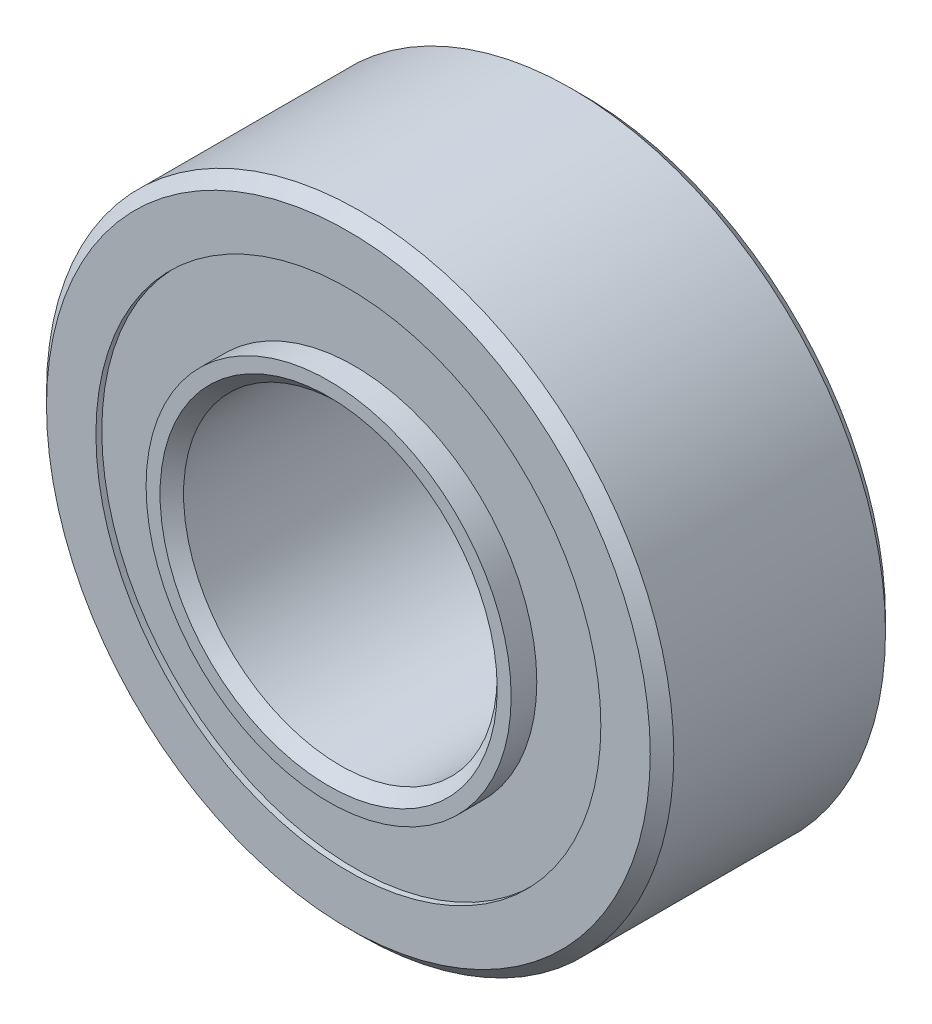
SolidWorks part; units mm, degrees
ref_plane "Front Plane" through (0, 0, 0) normal (0, 0, 1) x (1, 0, 0)
ref_plane "Top Plane" through (0, 0, 0) normal (0, 1, 0) x (1, 0, 0)
ref_plane "Right Plane" through (0, 0, 0) normal (1, 0, 0) x (0, 0, -1)
sketch "Sketch1" plane through (0, 0, 0) normal (1, 0, 0) x (0, 0, -1)
  line L0 (-2.3813, 0) -> (2.3813, 0) construction
  line L1 (0, 6.35) -> (0, -6.35) construction
  line L2 (2.1431, 6.35) -> (-2.1431, 6.35)
  line L3 (-2.1431, 6.35) -> (-2.3813, 6.1119)
  line L4 (-2.3813, 6.1119) -> (-2.3813, 5.1114)
  line L5 (-2.3813, 5.1114) -> (-1.0583, 5.1114)
  line L6 (2.3813, 5.1114) -> (1.0583, 5.1114)
  line L7 (2.3813, 6.1119) -> (2.3813, 5.1114)
  line L8 (2.1431, 6.35) -> (2.3813, 6.1119)
  line L9 (0, 6.35) -> (0, 4.7625) construction
  line L10 (0, 4.7625) -> (0, 3.175) construction
  arc A0 (-1.0583, 5.1114) -> (1.0583, 5.1114) centre (0, 4.7625) cw
  point P14 (0, 3.175)
  dimension "Width" = 4.7625
  dimension "OD" = 12.7
  dimension "D1" = 45
  dimension "D2" = 0.2381
  dimension "Shaft Dia" = 6.35
  dimension "D3" = 2.1167
  dimension "D4" = 0.3489
revolve "Revolve1" add sketch "Sketch1" angle 360 about L0
sketch "Sketch3" plane through (0, 0, 0) normal (1, 0, 0) x (0, 0, -1)
  line L0 (-1.0583, 4.4136) -> (-2.7813, 4.4136) construction
  line L1 (-2.3813, 6.1119) -> (-2.3813, 5.1114) construction
  line L2 (-2.1431, 6.35) -> (-2.3813, 6.1119) construction
  line L3 (-2.7813, 4.4136) -> (-2.7813, 3.4131) construction
  line L4 (-2.7813, 3.4131) -> (-2.7813, 3.6957)
  line L5 (-2.7813, 3.4131) -> (-2.5432, 3.175)
  line L6 (-2.5432, 3.175) -> (2.5432, 3.175)
  line L7 (-2.7813, 3.6957) -> (2.7813, 3.6957)
  line L8 (2.5432, 3.175) -> (2.7813, 3.4131)
  line L9 (-1.5875, 0) -> (1.3916, 0) construction
  line L10 (2.7813, 3.4131) -> (2.7813, 4.4136) construction
  line L11 (2.7813, 4.4136) -> (1.0583, 4.4136) construction
  line L12 (0, 6.35) -> (0, -6.35) construction
  line L13 (2.1431, 6.35) -> (2.3813, 6.1119) construction
  line L18 (2.7813, 3.6957) -> (2.7813, 3.4131)
  arc A1 (1.0583, 4.4136) -> (-1.0583, 4.4136) centre (0, 4.7625) cw construction
  arc A2 (1.0583, 5.1114) -> (-1.0583, 5.1114) centre (0, 4.7625) ccw construction
  dimension "D1" = 45
  dimension "Ring" = 5.5626
  dimension "D2" = 7.3914
revolve "Revolve3" add sketch "Sketch3" angle 360 about L0
sketch "Sketch4" plane through (0, 0, 0) normal (1, 0, 0) x (0, 0, -1)
  line L0 (-1.1144, 4.7625) -> (1.1144, 4.7625)
  arc A2 (-1.1144, 4.7625) -> (1.1144, 4.7625) centre (0, 4.7625) cw
  arc A3 (1.0583, 5.1114) -> (-1.0583, 5.1114) centre (0, 4.7625) ccw construction
revolve "Revolve4" add sketch "Sketch4" angle 360 about L0
ref_axis "Axis1" through (0, 0, -2.3813) along (0, 0, 1)
pattern_circular "CirPattern1" count 10 every 36 about axis through (0, 0, -2.3813) along (0, 0, 1) of bodies 104
sketch "Sketch5" plane through (0, 0, 0) normal (1, 0, 0) x (0, 0, -1)
  line L0 (-2.3813, 5.1114) -> (-1.0583, 5.1114) construction
  line L1 (-2.2622, 5.1114) -> (-1.1144, 5.1114)
  line L2 (-2.2622, 5.1114) -> (-2.2622, 3.6957)
  line L3 (-2.2622, 3.6957) -> (-1.1144, 3.6957)
  line L4 (-1.1144, 5.1114) -> (-1.1144, 3.6957)
  line L5 (-2.7813, 3.6957) -> (2.7813, 3.6957) construction
  line L6 (2.3813, 5.1114) -> (1.0583, 5.1114) construction
  line L7 (2.2622, 5.1114) -> (1.1144, 5.1114)
  line L8 (2.2622, 5.1114) -> (2.2622, 3.6957)
  line L9 (2.2622, 3.6957) -> (1.1144, 3.6957)
  line L10 (1.1144, 5.1114) -> (1.1144, 3.6957)
  line L12 (-2.1431, 6.35) -> (-2.3813, 6.1119) construction
  point P18 (-2.2622, 6.2309)
revolve "Revolve5" add sketch "Sketch5" angle 360 about L0
equation "\"D2@Sketch1\" = \"Width@Sketch1\"*.05"
equation "\"D3@Sketch1\" = \"Width@Sketch1\"/2.25"
equation "\"D4@Sketch1\" = (((\"OD@Sketch1\"-\"Width@Sketch1\")/2)/3.25)/3.5"
equation "\"D2@CirPattern1\" = 360/\"Balls@CirPattern1\""
